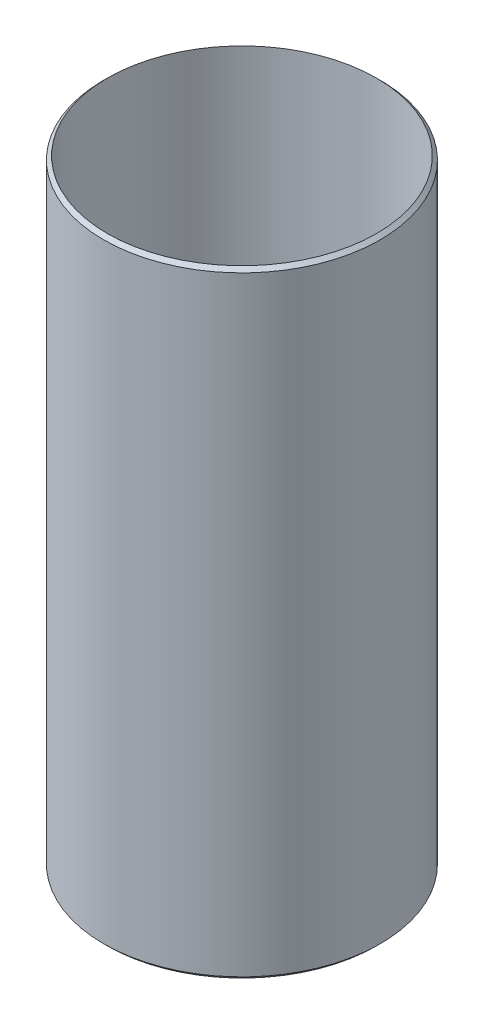
SolidWorks part; units mm, degrees
material "Plain Carbon Steel"
ref_plane "Front Plane" through (0, 0, 0) normal (0, 0, 1) x (1, 0, 0)
ref_plane "Top Plane" through (0, 0, 0) normal (0, 1, 0) x (1, 0, 0)
ref_plane "Right Plane" through (0, 0, 0) normal (1, 0, 0) x (0, 0, -1)
sketch "Sketch1" plane through (0, 0, 0) normal (0, 1, 0) x (1, 0, 0)
  circle A0 centre (0, 0) radius 74.2
  circle A1 centre (0, 0) radius 76.2
  dimension "D1" = 152.4
  dimension "D2" = 2
extrude "Boss-Extrude1" add sketch "Sketch1" along normal blind 340
chamfer "Chamfer1" distance 2 angle 45 2 edges at (0, 0, 76.2) (0, 340, 76.2)
equation "\"TubeDiameter\" = 6.000in"
equation "\"D1@Sketch1\"=\"TubeDiameter\""
